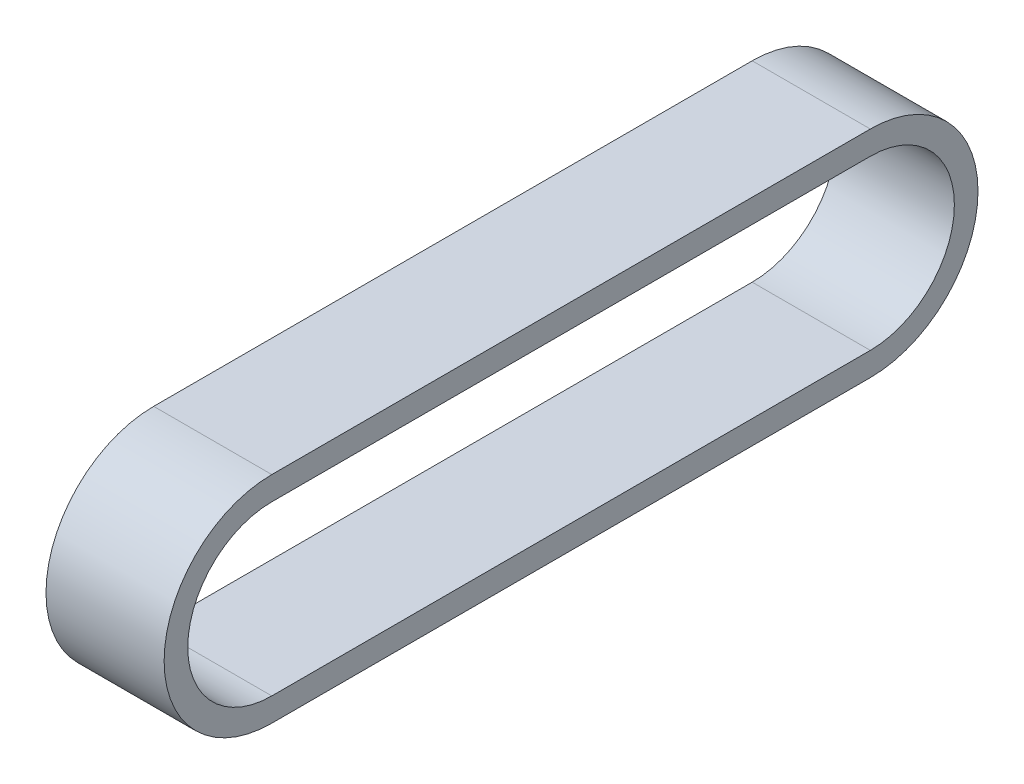
SolidWorks part; units mm, degrees
ref_plane "Front Plane" through (0, 0, 0) normal (0, 0, 1) x (1, 0, 0)
ref_plane "Top Plane" through (0, 0, 0) normal (0, 1, 0) x (1, 0, 0)
ref_plane "Right Plane" through (0, 0, 0) normal (1, 0, 0) x (0, 0, -1)
sketch "스케치2" plane through (0, 0, 0) normal (1, 0, 0) x (0, 0, -1)
  line L0 (0, 0) -> (50000, 0) construction
  line L1 (-76, 0) -> (-76, -50000) construction
  line L2 (76, 0) -> (76, -50000) construction
  line L3 (0, 0) -> (0, -50000) construction
  line L4 (-76, 27.345) -> (76, 27.345)
  line L5 (-76, -27.345) -> (76, -27.345)
  arc A0 (-76, 27.345) -> (-76, -27.345) centre (-76, 0) ccw
  arc A1 (76, -27.345) -> (76, 27.345) centre (76, 0) ccw
  dimension "D1" = 76
  dimension "D2" = 76
extrude "보스-돌출1" add sketch "스케치2" along normal blind 15 and the other way blind 15
sketch "스케치3" plane through (15, 0, 0) normal (1, 0, 0) x (0, 0, -1)
  line L0 (0, 0) -> (50000, 0) construction
  line L1 (76, 0) -> (76, 50000) construction
  line L2 (-76, 0) -> (-76, 50000) construction
  line L3 (-76, 21.345) -> (76, 21.345)
  line L4 (-76, -21.345) -> (76, -21.345)
  arc A0 (-76, 21.345) -> (-76, -21.345) centre (-76, 0) ccw
  arc A1 (76, -21.345) -> (76, 21.345) centre (76, 0) ccw
extrude "컷-돌출1" cut sketch "스케치3" against normal blind 30
